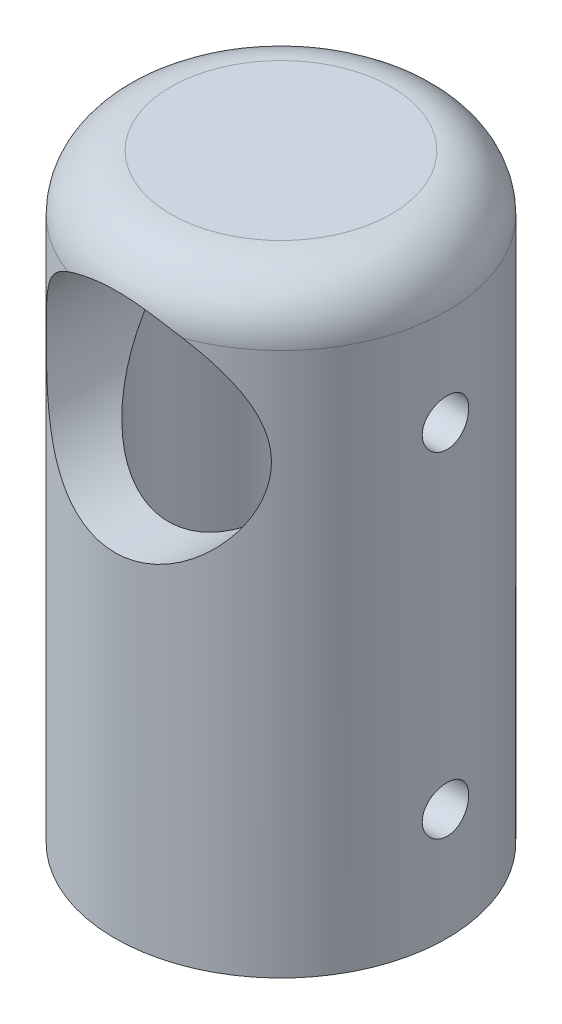
SolidWorks part; units mm, degrees
material "6061 合金"
ref_plane "前视基准面" through (0, 0, 0) normal (0, 0, 1) x (1, 0, 0)
ref_plane "上视基准面" through (0, 0, 0) normal (0, 1, 0) x (1, 0, 0)
ref_plane "右视基准面" through (0, 0, 0) normal (1, 0, 0) x (0, 0, -1)
sketch "草图1" plane through (0, 0, 0) normal (0, 0, 1) x (1, 0, 0)
  line L0 (6.05, 0) -> (8.925, 0)
  line L2 (8.9254, 0) -> (8.925, 0)
  line L3 (8.925, 0) -> (8.925, 32.2)
  line L4 (8.925, 32.2) -> (0, 32.2)
  line L5 (0, 32.2) -> (0, 30.05) construction
  line L6 (6.05, 0) -> (6.05, 24)
  arc A0 (0, 30.05) -> (6.05, 24) centre (0, 24) cw
  point P10 (8.9254, 0)
  point P11 (8.6627, 0)
  dimension "D1" = 24
  dimension "D2" = 12.1
  dimension "D3" = 32.2
  dimension "D6" = 17.85
revolve "旋转1" add sketch "草图1" angle 360 about L5 region at (6.7827, 18.6953, 0)
sketch "草图2" plane through (0, 0, 0) normal (0, 0, 1) x (1, 0, 0)
  circle A0 centre (0, 24) radius 6.05
  dimension "D1" = 12.1
extrude "切除-拉伸1" cut sketch "草图2" against normal through all both and the other way through all
hole_wizard "M3 螺纹孔1" positions "草图3" profile "草图4" tap size "M3" standard "GB" end condition through all
sketch "草图3" plane through (0, 0, 0) normal (1, 0, 0) x (0, 0, -1)
  line L1 (-8.925, 0) -> (8.925, 0) construction
  line L3 (0, 0) -> (0, 24) construction
  point P0 (0, 6)
  point P12 (0, 24)
  point P20 (0, 6)
  point P21 (0, 6)
  dimension "D1" = 6
  dimension "D2" = 24
cosmetic thread "孔螺蚊线1" parameters "D2"=3
sketch "草图4" plane through (0, 6, 0) normal (0, 1, 0) x (0, 0, 1)
  line L0 (0, 0) -> (0, 8.925)
  line L1 (0, 8.925) -> (1.25, 8.925)
  line L2 (1.25, 8.925) -> (1.25, 0)
  line L5 (1.25, 0) -> (0, 0)
  line L11 (0, -6.35) -> (0, 107.95) construction
  dimension "通孔螺纹孔钻头直径" = 2.5
  dimension "通孔螺纹孔钻头深度" = 8.925
cosmetic thread "孔螺蚊线6" parameters "D2"=3
mirror "镜向1" about plane through (0, 0, 0) normal (1, 0, 0) of "M3 螺纹孔1"
fillet "圆角1" radius 3 1 edges at (-8.925, 32.2, 0)
